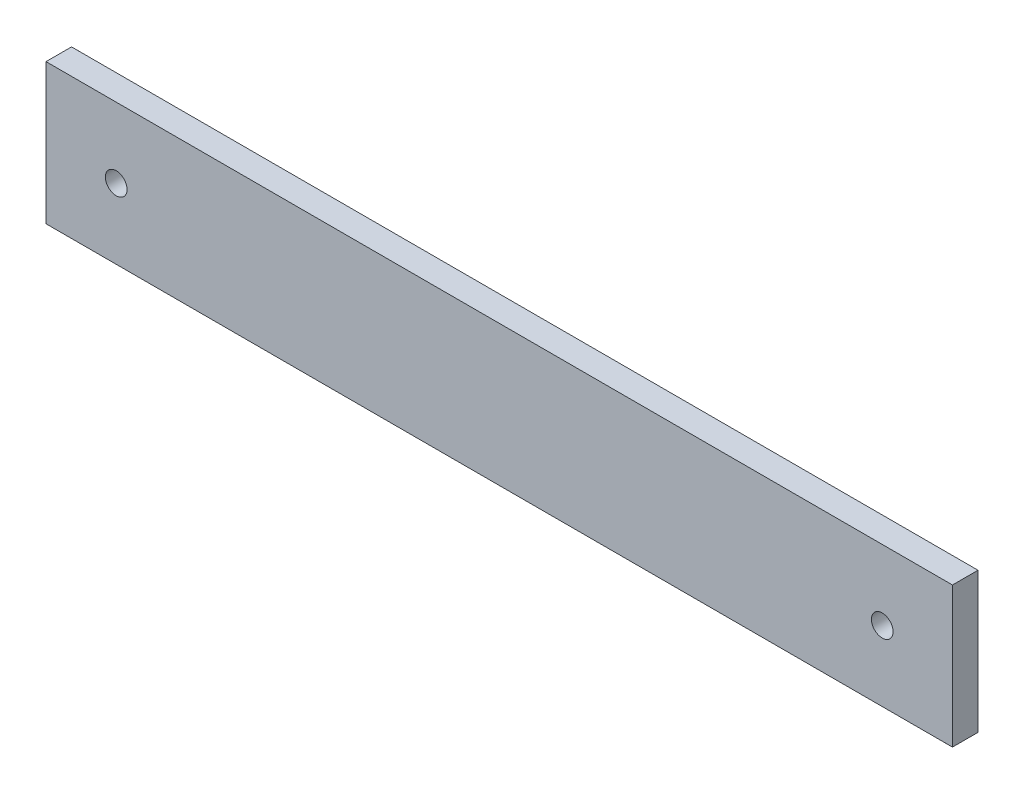
SolidWorks part; units mm, degrees
ref_plane "前视基准面" through (0, 0, 0) normal (0, 0, 1) x (1, 0, 0)
ref_plane "上视基准面" through (0, 0, 0) normal (0, 1, 0) x (1, 0, 0)
ref_plane "右视基准面" through (0, 0, 0) normal (1, 0, 0) x (0, 0, -1)
other "Configuration Table"
sketch "草图1" plane through (0, 0, 0) normal (0, 0, 1) x (1, 0, 0)
  line L1 (-11, -11) -> (131, -11)
  line L2 (-11, -11) -> (-11, 11)
  line L3 (-11, 11) -> (131, 11)
  line L4 (131, -11) -> (131, 11)
  line L5 (-11, -11) -> (131, 11) construction
  line L6 (-11, 11) -> (131, -11) construction
  circle A0 centre (0, 0) radius 1.7
  circle A1 centre (120, 0) radius 1.7
extrude "凸台-拉伸1" add sketch "草图1" along normal mid plane 4
